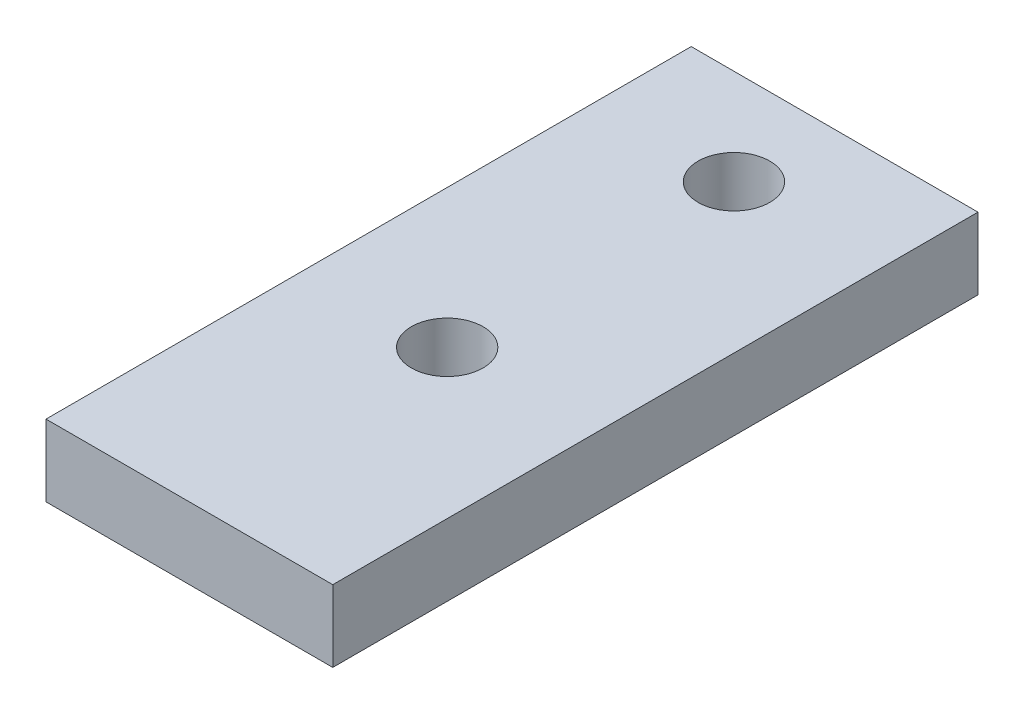
SolidWorks part; units mm, degrees
ref_plane "Płaszczyzna przednia" through (0, 0, 0) normal (0, 0, 1) x (1, 0, 0)
ref_plane "Płaszczyzna górna" through (0, 0, 0) normal (0, 1, 0) x (1, 0, 0)
ref_plane "Płaszczyzna prawa" through (0, 0, 0) normal (1, 0, 0) x (0, 0, -1)
sketch "Szkic1" plane through (0, 0, 0) normal (0, 1, 0) x (1, 0, 0)
  line L1 (0, 0) -> (40, 0)
  line L2 (0, 0) -> (0, 90)
  line L3 (0, 90) -> (40, 90)
  line L4 (40, 0) -> (40, 90)
  circle A0 centre (19.31, 76.65) radius 5
  circle A1 centre (19.31, 36.65) radius 5
  point P9 (0, 0)
  dimension "D3" = 10
  dimension "D5" = 20.69
  dimension "D6" = 40
  dimension "D1" = 40
  dimension "D2" = 90
  dimension "D4" = 13.35
extrude "Dodanie-wyciągnięcie1" add sketch "Szkic1" along normal blind 10
